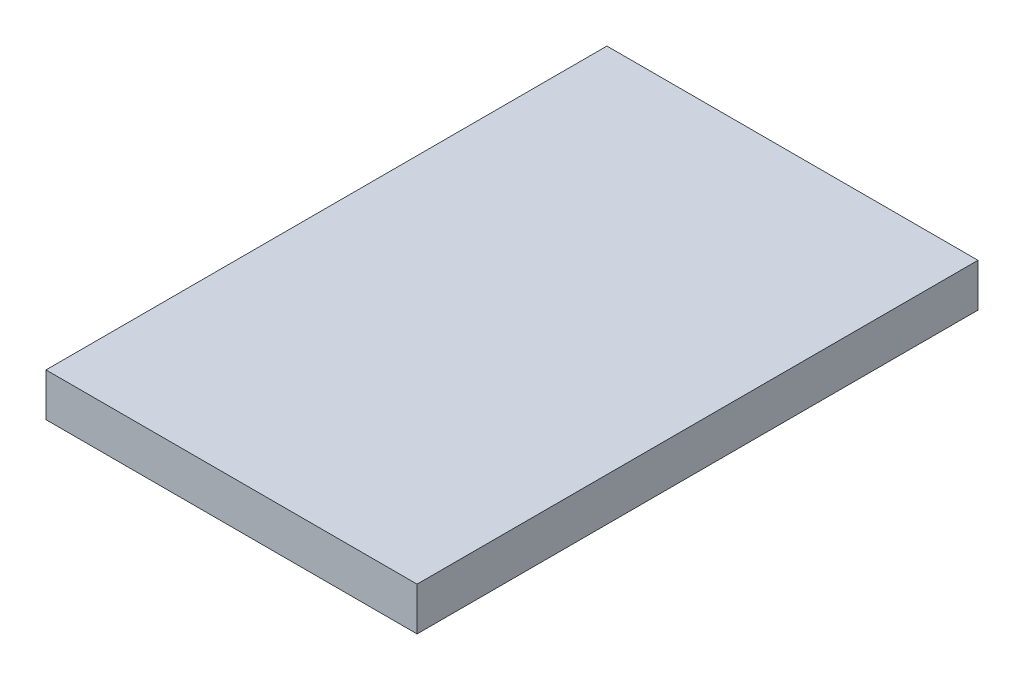
SolidWorks part; units mm, degrees
ref_plane "Front Plane" through (0, 0, 0) normal (0, 0, 1) x (1, 0, 0)
ref_plane "Top Plane" through (0, 0, 0) normal (0, 1, 0) x (1, 0, 0)
ref_plane "Right Plane" through (0, 0, 0) normal (1, 0, 0) x (0, 0, -1)
sketch "Sketch1" plane through (0, 0, 0) normal (0, 1, 0) x (1, 0, 0)
  line L1 (0, 0) -> (-54.61, 0)
  line L2 (0, 0) -> (0, 82.55)
  line L3 (0, 82.55) -> (-54.61, 82.55)
  line L4 (-54.61, 0) -> (-54.61, 82.55)
  dimension "D1" = 82.55
  dimension "D2" = 54.61
extrude "Boss-Extrude1" add sketch "Sketch1" along normal blind 6.35
ref_plane "KORAL!!!" through (-27.305, 0, 0) normal (1, 0, 0) x (0, 0, -1)
